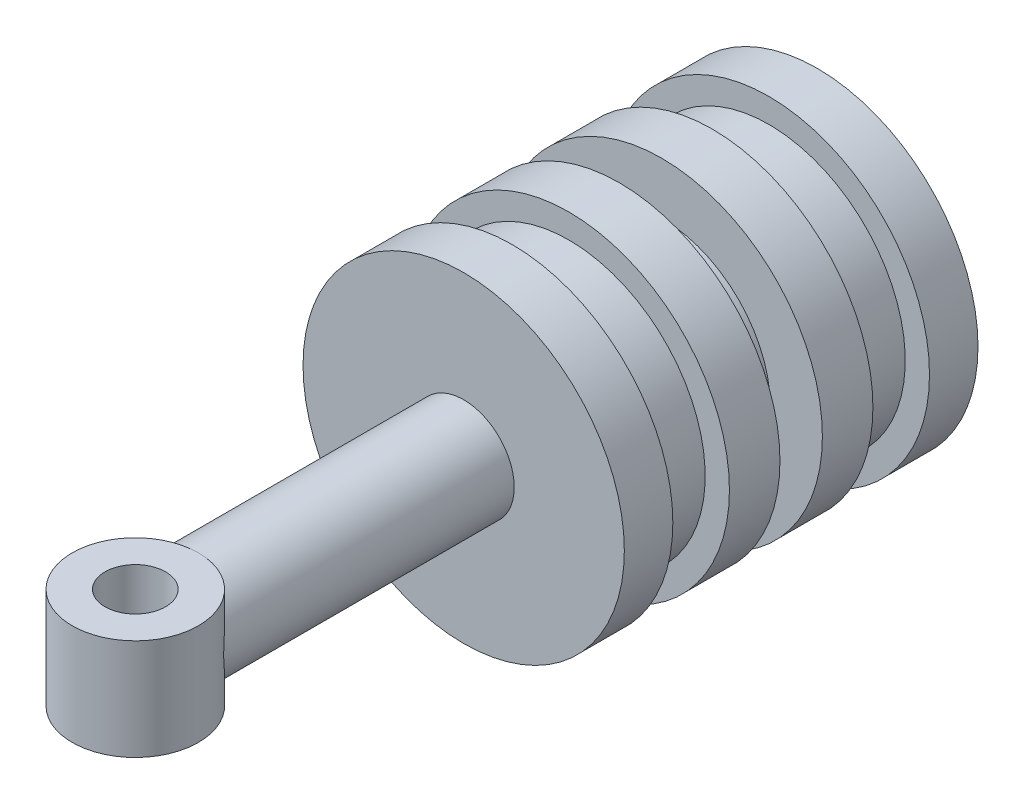
SolidWorks part; units mm, degrees
ref_plane "Front Plane" through (0, 0, 0) normal (0, 0, 1) x (1, 0, 0)
ref_plane "Top Plane" through (0, 0, 0) normal (0, 1, 0) x (1, 0, 0)
ref_plane "Right Plane" through (0, 0, 0) normal (1, 0, 0) x (0, 0, -1)
sketch "Sketch3" plane through (0, 0, 0) normal (0, 0, 1) x (1, 0, 0)
  circle A0 centre (0, 0) radius 15.9
  dimension "D1" = 31.8
extrude "Boss-Extrude1" add sketch "Sketch3" along normal blind 35
sketch "Sketch4" plane through (0, 0, 35) normal (0, 0, 1) x (1, 0, 0)
  circle A0 centre (0, 0) radius 5
  dimension "D1" = 10
extrude "Boss-Extrude2" add sketch "Sketch4" along normal blind 32.5
sketch "Sketch7" plane through (0, 0, 0) normal (1, 0, 0) x (0, 0, -1)
  line L0 (0, 15.9) -> (-35, 15.9) construction
  line L1 (-19.6, 15.9) -> (-15.4, 15.9)
  line L2 (-19.6, 15.9) -> (-19.6, 10.75)
  line L3 (-19.6, 10.75) -> (-15.4, 10.75)
  line L4 (-15.4, 15.9) -> (-15.4, 10.75)
  line L6 (-35, 15.9) -> (-35, -15.9) construction
  line L8 (0, 15.9) -> (-35, 15.9) construction
  line L9 (11.9985, 0) -> (-52.5548, 0) construction
  line L10 (0, -15.9) -> (0, 15.9) construction
  line L11 (-30.2, 15.9) -> (-24.6, 15.9)
  line L12 (-30.2, 15.9) -> (-30.2, 13.5)
  line L13 (-30.2, 13.5) -> (-24.6, 13.5)
  line L14 (-24.6, 15.9) -> (-24.6, 13.5)
  line L15 (-10.4, 15.9) -> (-4.8, 15.9)
  line L16 (-10.4, 15.9) -> (-10.4, 13.5)
  line L17 (-10.4, 13.5) -> (-4.8, 13.5)
  line L18 (-4.8, 15.9) -> (-4.8, 13.5)
  point P10 (-17.5, 15.9)
  dimension "D2" = 4.2
  dimension "D3" = 5.15
  dimension "D4" = 5.6
  dimension "D5" = 5.6
  dimension "D6" = 2.4
  dimension "D7" = 2.4
  dimension "D8" = 5
  dimension "D9" = 5
revolve "Cut-Revolve1" cut sketch "Sketch7" angle 360 about L9
sketch "Sketch8" plane through (0, 0, 0) normal (0, 1, 0) x (1, 0, 0)
  line L0 (-5, -67.5) -> (5, -67.5) construction
  circle A0 centre (0, -67.5) radius 6.25
  circle A1 centre (0, -67.5) radius 3
  point P5 (0, -67.5)
  dimension "D1" = 12.5
  dimension "D2" = 6
extrude "Boss-Extrude3" add sketch "Sketch8" along normal blind 5 and the other way blind 5
sketch "Sketch9" plane through (0, 5, 0) normal (0, 1, 0) x (1, 0, 0)
  line L0 (-3, -67.5) -> (3, -67.5) construction
  circle A0 centre (0, -67.5) radius 3
  dimension "D1" = 6
extrude "Cut-Extrude1" cut sketch "Sketch9" against normal blind 16
